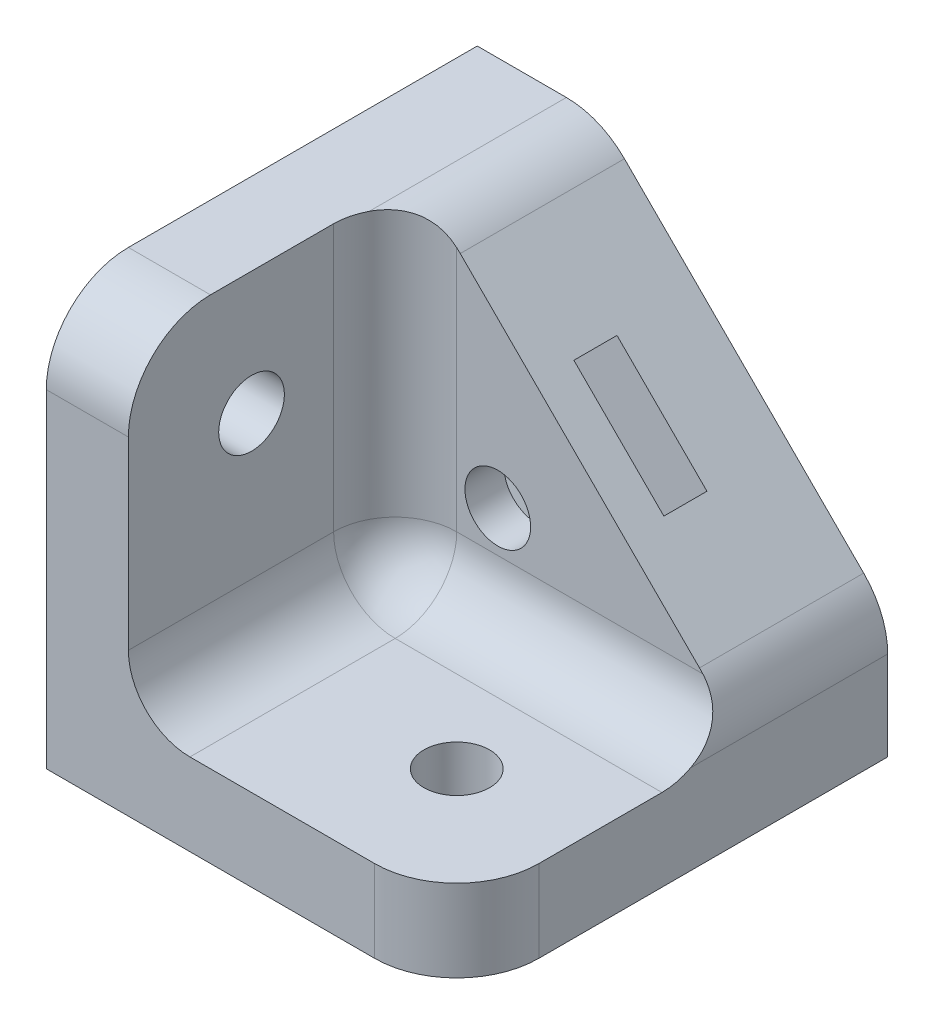
SolidWorks part; units mm, degrees
ref_plane "Front Plane" through (0, 0, 0) normal (0, 0, 1) x (1, 0, 0)
ref_plane "Top Plane" through (0, 0, 0) normal (0, 1, 0) x (1, 0, 0)
ref_plane "Right Plane" through (0, 0, 0) normal (1, 0, 0) x (0, 0, -1)
sketch "Sketch4" plane through (0, 0, 0) normal (0, 0, 1) x (1, 0, 0)
  line L2 (0, 0) -> (0, 20)
  line L3 (0, 20) -> (4, 20)
  line L4 (4, 4) -> (4, 20)
  line L5 (0, 0) -> (20, 0)
  line L7 (4, 4) -> (20, 4)
  line L8 (20, 0) -> (20, 4)
  line L9 (4, 20) -> (6, 20)
  line L10 (6, 20) -> (20, 6)
  line L11 (20, 6) -> (20, 4)
  point P3 (0, 0)
  dimension "D1" = 4
  dimension "D2" = 4
  dimension "D3" = 20
  dimension "D4" = 20
  dimension "D5" = 2
  dimension "D6" = 2
extrude "Boss-Extrude4" add sketch "Sketch4" along normal blind 8 separate body contours L5 L8 L7 L4 L3 L2 | L4 L7 region at (0.2828, 10, 0) region at (9.9325, 9.9325, 0)
extrude "Boss-Extrude5" add sketch "Sketch4<4>" along normal blind 21 contours L5 L8 L7 L4 L3 L2 region at (0.2828, 10, 0)
sketch "Sketch4<4>" plane through (0, 0, 0) normal (0, 0, 1) x (1, 0, 0) same geometry as "Sketch4"
sketch "Sketch5" plane through (13, 13, 0) normal (0.7071, 0.7071, 0) x (0, 0, -1)
  line L1 (-6.1, -3.1) -> (-4, -3.1)
  line L2 (-6.1, -3.1) -> (-6.1, 3.1)
  line L3 (-6.1, 3.1) -> (-4, 3.1)
  line L4 (-4, -3.1) -> (-4, 3.1)
  line L5 (-6.1, -3.1) -> (-4, 3.1) construction
  line L6 (-6.1, 3.1) -> (-4, -3.1) construction
  line L8 (0, 9.8995) -> (0, -9.8995) construction
  point P0 (-5.05, 0)
  point P10 (0, -15.3082)
  dimension "D1" = 2.1
  dimension "D2" = 4
  dimension "D3" = 6.2
extrude "Cut-Extrude1" cut sketch "Sketch5" against normal blind 9
hole_wizard "Ø3.2 (3.2) Diameter Hole1" positions "3DSketch2" profile "Sketch6" hole size "Ø3.2" standard "ANSI Metric" end condition through all
sketch3d "3DSketch2"
  line L0 (0, 0, 21) -> (0, 0, 0) construction
  line L1 (0, 0, 0) -> (20, 0, 0) construction
  line L2 (0, 0, 0) -> (0, 20, 0) construction
  point P0 (14, 0, 15)
  point P2 (0, 14, 15)
  point P4 (9, 9, 0)
  dimension "D1" = 14
  dimension "D2" = 14
  dimension "D3" = 15
  dimension "D4" = 15
  dimension "D5" = 9
  dimension "D6" = 9
sketch "Sketch6" plane through (14, 0, 15) normal (1, 0, 0) x (0, 0, -1)
  line L0 (0, 0) -> (0, 20)
  line L1 (0, 20) -> (1.6, 20)
  line L2 (1.6, 20) -> (1.6, 0)
  line L5 (1.6, 0) -> (0, 0)
  line L11 (0, -6.35) -> (0, 107.95) construction
  dimension "Thru Hole Dia." = 3.2
  dimension "Thru Hole Depth" = 20
chamfer "Chamfer1" distance 1.5 angle 45 2 edges at (4.444, 8.8281, 5.05) (8.8281, 4.444, 5.05)
fillet "Fillet1" radius 3 3 edges at (12, 4, 8) (4, 4, 14.5) (4, 12, 8)
fillet "Fillet2" radius 4 4 edges at (6, 20, 4.0858) (20, 6, 4.0858) (20, 2, 21) (2, 20, 21)
equation "\"D2@Sketch4\"=\"D1@Sketch4\""
equation "\"D4@Sketch4\"=\"D3@Sketch4\""
equation "\"D6@Sketch4\"=\"D5@Sketch4\""
